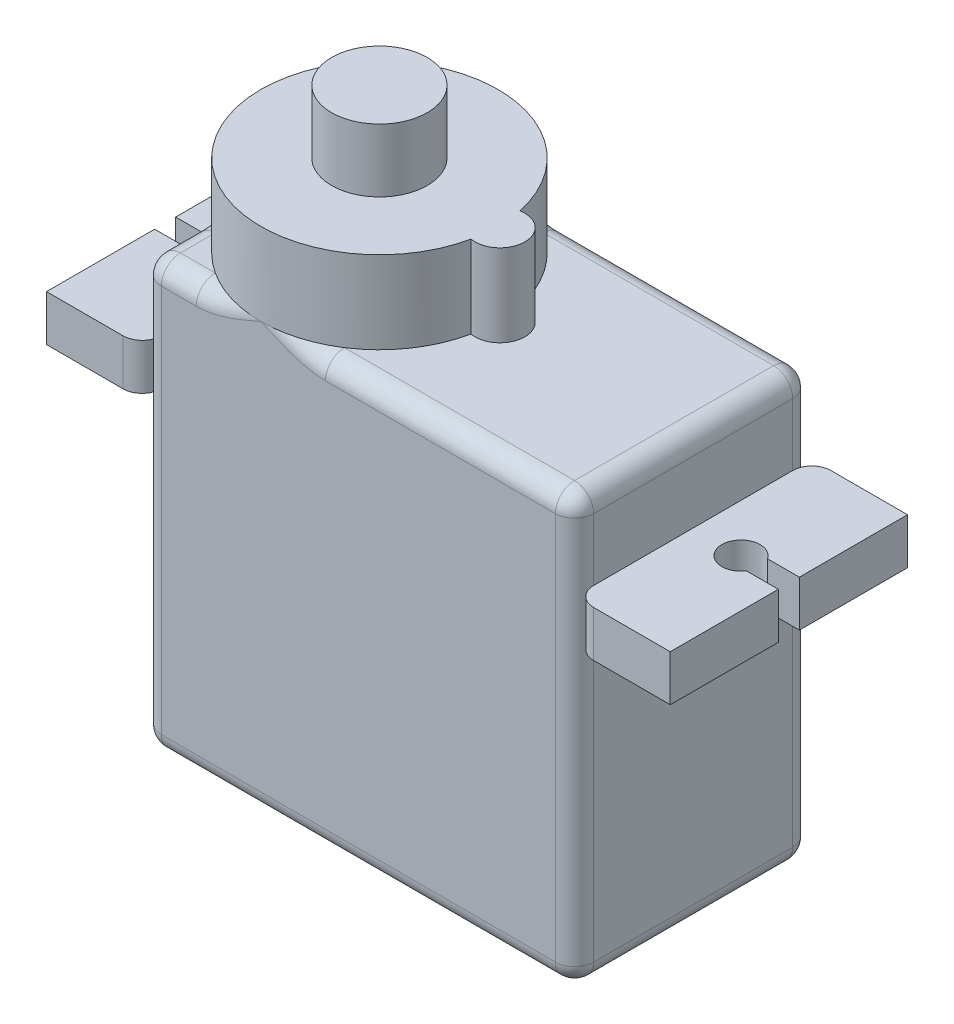
SolidWorks part; units mm, degrees
ref_plane "Front Plane" through (0, 0, 0) normal (0, 0, 1) x (1, 0, 0)
ref_plane "Top Plane" through (0, 0, 0) normal (0, 1, 0) x (1, 0, 0)
ref_plane "Right Plane" through (0, 0, 0) normal (1, 0, 0) x (0, 0, -1)
sketch "Sketch1" plane through (0, 0, 0) normal (0, 1, 0) x (1, 0, 0)
  line L1 (-11.3, -6.2) -> (11.3, -6.2)
  line L2 (-11.3, -6.2) -> (-11.3, 6.2)
  line L3 (-11.3, 6.2) -> (11.3, 6.2)
  line L4 (11.3, -6.2) -> (11.3, 6.2)
  line L5 (-11.3, -6.2) -> (11.3, 6.2) construction
  line L6 (-11.3, 6.2) -> (11.3, -6.2) construction
  point P0 (0, 0)
  dimension "D1" = 22.6
  dimension "D2" = 12.4
extrude "Boss-Extrude1" add sketch "Sketch1" along normal blind 22.3
sketch "Sketch2" plane through (-11.3, 0, 0) normal (-1, 0, 0) x (0, 0, 1)
  line L0 (-6.2, 22.3) -> (-6.2, 0) construction
  line L1 (-6.2, 18.05) -> (6.2, 18.05)
  line L2 (-6.2, 18.05) -> (-6.2, 15.65)
  line L3 (-6.2, 15.65) -> (6.2, 15.65)
  line L4 (6.2, 18.05) -> (6.2, 15.65)
  line L5 (6.2, 22.3) -> (6.2, 0) construction
  line L6 (-6.2, 22.3) -> (6.2, 22.3) construction
  dimension "D1" = 2.4
  dimension "D2" = 4.25
extrude "Boss-Extrude2" add sketch "Sketch2" along normal blind 5 separate body
sketch "Sketch3" plane through (11.3, 0, 0) normal (1, 0, 0) x (0, 0, -1)
  line L0 (-6.2, 22.3) -> (-6.2, 0) construction
  line L1 (-6.2, 18.05) -> (6.2, 18.05)
  line L2 (-6.2, 18.05) -> (-6.2, 15.65)
  line L3 (-6.2, 15.65) -> (6.2, 15.65)
  line L4 (6.2, 18.05) -> (6.2, 15.65)
  line L5 (6.2, 22.3) -> (6.2, 0) construction
  line L6 (-6.2, 22.3) -> (6.2, 22.3) construction
  dimension "D1" = 2.4
  dimension "D2" = 4.25
extrude "Boss-Extrude3" add sketch "Sketch3" along normal blind 5 separate body
sketch "Sketch4" plane through (0, 18.05, 0) normal (0, 1, 0) x (1, 0, 0)
  line L0 (16.3, 0) -> (-16.3, 0) construction
  line L1 (16.3, 6.2) -> (16.3, -6.2) construction
  line L2 (-16.3, -6.2) -> (-16.3, 6.2) construction
  line L6 (-16.3, 0.55) -> (-14.6352, 0.55)
  line L7 (-16.3, 0.55) -> (-16.3, -0.55)
  line L8 (-16.3, -0.55) -> (-14.6352, -0.55)
  line L9 (0, 0) -> (0, 6.2) construction
  line L10 (11.3, 6.2) -> (-11.3, 6.2) construction
  line L11 (16.3, 0.55) -> (14.6352, 0.55)
  line L12 (16.3, -0.55) -> (14.6352, -0.55)
  line L13 (16.3, 0.55) -> (16.3, -0.55)
  arc A1 (-14.6352, -0.55) -> (-14.6352, 0.55) centre (-13.8, 0) ccw
  arc A2 (14.6352, -0.55) -> (14.6352, 0.55) centre (13.8, 0) cw
  dimension "D1" = 2
  dimension "D2" = 1.1
  dimension "D3" = 0.55
  dimension "D4" = 2.5
extrude "Cut-Extrude1" cut sketch "Sketch4" against normal blind 5
sketch "Sketch5" plane through (0, 22.3, 0) normal (0, 1, 0) x (1, 0, 0)
  line L0 (-11.3, 6.2) -> (-11.3, -6.2) construction
  arc A2 (0.9667, 1.2789) -> (0.9667, -1.2789) centre (-5.1, 0) ccw
  arc A3 (0.9667, -1.2789) -> (0.9667, 1.2789) centre (1.2, 0) ccw
  dimension "D1" = 1.3
  dimension "D2" = 6.2
  dimension "D3" = 6.3
  dimension "D4" = 6.2
  dimension "D5" = 1.2
extrude "Boss-Extrude4" add sketch "Sketch5" along normal blind 4.3
sketch "Sketch6" plane through (0, 26.6, 0) normal (0, 1, 0) x (1, 0, 0)
  circle A0 centre (-5.1, 0) radius 2.5
  dimension "D1" = 5
extrude "Boss-Extrude5" add sketch "Sketch6" along normal blind 3.3
sketch "Sketch7" plane through (-11.3, 0, 0) normal (-1, 0, 0) x (0, 0, 1)
  circle A0 centre (0, 4.5) radius 0.6
  circle A1 centre (-1.2, 4.5) radius 0.6
  circle A2 centre (1.2, 4.5) radius 0.6
  dimension "D1" = 1.2
  dimension "D2" = 4.5
extrude "Boss-Extrude6" add sketch "Sketch7" along normal blind 2.3 separate body contours A1 | A0 | A2 region at (-11.3, 4.5, 0) region at (-11.3, 4.5, -1.2) region at (-11.3, 4.5, 1.2)
fillet "Fillet1" radius 1 15 edges at (-11.3, 22.3, 3.1) (-8.2, 22.3, -6.2) (-8.2, 22.3, 6.2) (11.3, 0, 0) (11.3, 11.15, -6.2) (0, 0, -6.2) (-11.3, 11.15, -6.2) (-11.3, 0, 0) (0, 0, 6.2) (11.3, 11.15, 6.2) (-11.3, 11.15, 6.2) (-11.3, 22.3, -3.1) (3.1, 22.3, -6.2) (11.3, 22.3, 0) (3.1, 22.3, 6.2)
fillet "Fillet2" radius 1 2 edges at (11.3, 16.85, -6.2) (11.3, 16.85, 6.2)
fillet "Fillet3" radius 1 2 edges at (-11.3, 16.85, 6.2) (-11.3, 16.85, -6.2)
